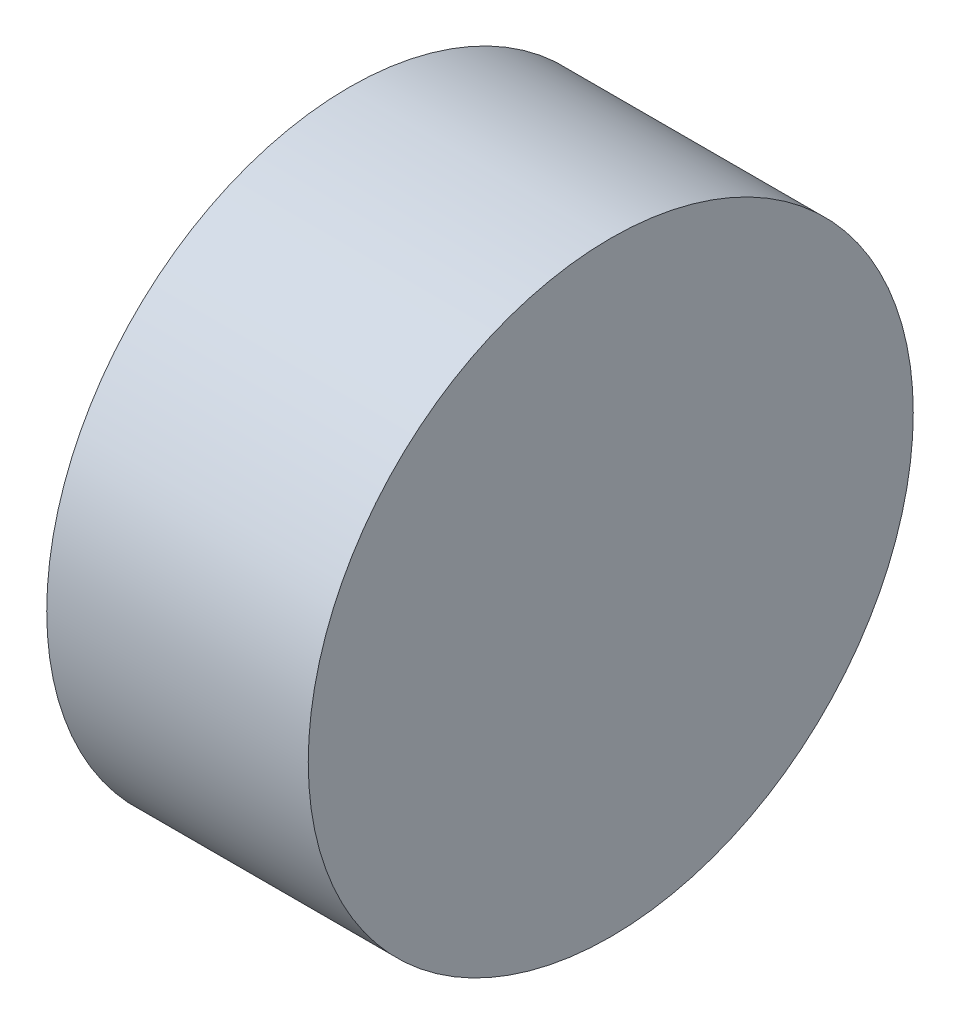
SolidWorks part; units mm, degrees
ref_plane "Front Plane" through (0, 0, 0) normal (0, 0, 1) x (1, 0, 0)
ref_plane "Top Plane" through (0, 0, 0) normal (0, 1, 0) x (1, 0, 0)
ref_plane "Right Plane" through (0, 0, 0) normal (1, 0, 0) x (0, 0, -1)
sketch "Sketch1" plane through (0, 0, 0) normal (1, 0, 0) x (0, 0, -1)
  circle A0 centre (0, 0) radius 11.5682
extrude "Boss-Extrude1" add sketch "Sketch1" along normal blind 10
